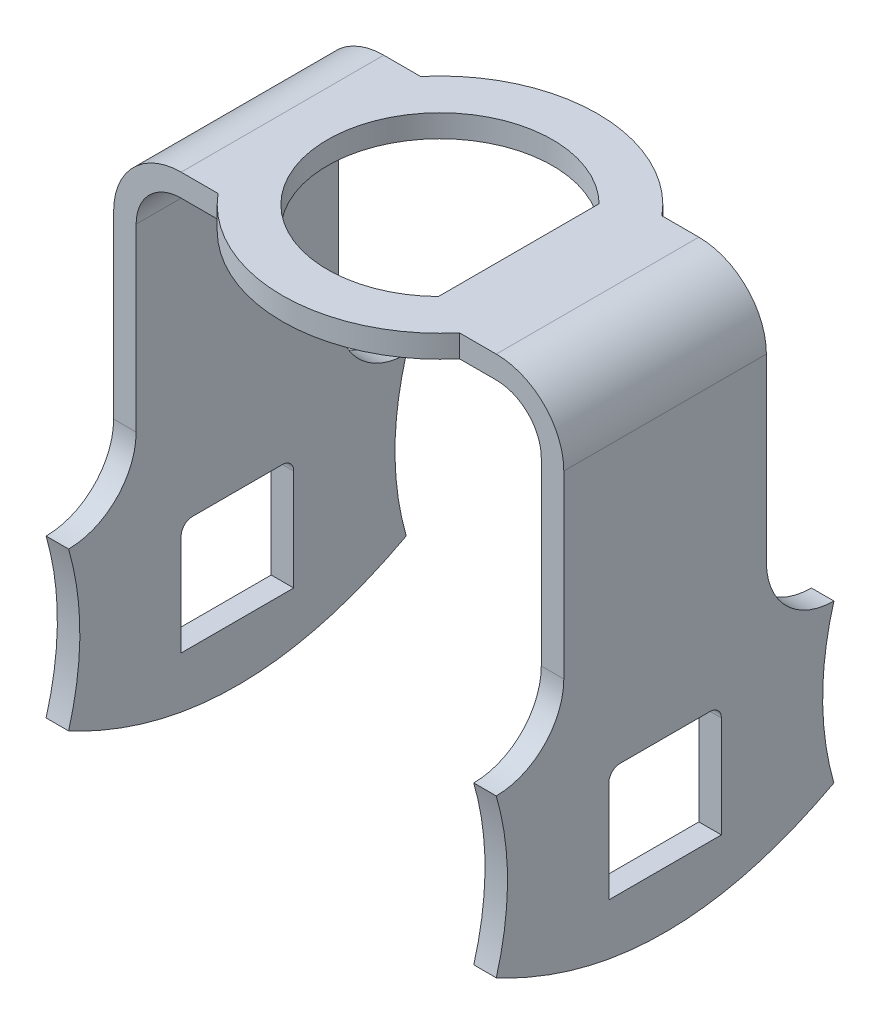
SolidWorks part; units mm, degrees
ref_plane "Front Plane" through (0, 0, 0) normal (0, 0, 1) x (1, 0, 0)
ref_plane "Top Plane" through (0, 0, 0) normal (0, 1, 0) x (1, 0, 0)
ref_plane "Right Plane" through (0, 0, 0) normal (1, 0, 0) x (0, 0, -1)
sketch "Sketch1" plane through (0, 0, 0) normal (0, 0, 1) x (1, 0, 0)
  line L0 (-19, 0) -> (-19, 20)
  line L1 (0, 0) -> (-1, 0)
  line L2 (0, 0) -> (0, 20)
  line L3 (-3, 23) -> (-17, 23)
  line L4 (-20, 0) -> (-20, 20)
  line L5 (-3, 22) -> (-17, 22)
  line L6 (-1, 0) -> (-1, 20)
  line L7 (-19, 0) -> (-20, 0)
  arc A0 (-17, 23) -> (-20, 20) centre (-17, 20) ccw
  arc A1 (0, 20) -> (-3, 23) centre (-3, 20) ccw
  arc A2 (-17, 22) -> (-19, 20) centre (-17, 20) ccw
  arc A3 (-1, 20) -> (-3, 22) centre (-3, 20) ccw
  point P7 (-20, 23)
  point P10 (0, 23)
  dimension "D3" = 3
  dimension "D4" = 3
  dimension "D1" = 23
  dimension "D2" = 20
  dimension "D5" = 1
extrude "Boss-Extrude1" add sketch "Sketch1" along normal blind 15
sketch "Sketch2" plane through (0, 23, 0) normal (0, 1, 0) x (1, 0, 0)
  line L0 (-10, 0) -> (-10, -15) construction
  line L1 (-3, 0) -> (-17, 0) construction
  line L2 (-3, -15) -> (-17, -15) construction
  line L3 (-6.5, -11.0707) -> (-6.5, -3.9293)
  arc A0 (-6.5, -3.9293) -> (-6.5, -11.0707) centre (-10, -7.5) ccw
  dimension "D1" = 10
  dimension "D2" = 3.5
extrude "Cut-Extrude2" cut sketch "Sketch2" against normal through all
sketch "Sketch4" plane through (0, 23, 0) normal (0, 1, 0) x (1, 0, 0)
  line L0 (0, -7.5) -> (-20, -7.5) construction
  line L1 (0, -15) -> (0, 0) construction
  line L2 (-20, -15) -> (-20, 0) construction
  line L3 (-4.6381, -12) -> (0, -12)
  line L4 (-4.6381, -3) -> (0, -3)
  line L5 (-10, 0) -> (-10, -15) construction
  line L6 (-3, 0) -> (-17, 0) construction
  line L7 (-3, -15) -> (-17, -15) construction
  line L8 (-15.3619, -12) -> (-20, -12)
  line L9 (-15.3619, -3) -> (-20, -3)
  line L10 (-20, -3) -> (-20, 0)
  line L11 (-20, 0) -> (0, 0)
  line L12 (0, 0) -> (0, -3)
  line L13 (-20, -12) -> (-20, -15)
  line L14 (-20, -15) -> (0, -15)
  line L15 (0, -15) -> (0, -12)
  arc A0 (-15.3619, -12) -> (-4.6381, -12) centre (-10, -7.5) ccw
  arc A1 (-4.6381, -3) -> (-15.3619, -3) centre (-10, -7.5) ccw
  dimension "D1" = 14
  dimension "D2" = 4.5
  dimension "D3" = 4.5
extrude "Cut-Extrude3" cut sketch "Sketch4" against normal blind 14
sketch "Sketch5" plane through (-20, 0, 0) normal (-1, 0, 0) x (0, 0, 1)
  line L0 (15, 0) -> (0, 0) construction
  line L1 (0, 0) -> (0, 2)
  line L2 (0, 9) -> (0, 0) construction
  line L3 (15, 9) -> (15, 0) construction
  line L4 (0, 2) -> (0, 0)
  line L5 (15, 0) -> (15, 2)
  spline S0 degree 2 poles (0, 2) (7.5, -2) (15, 2) knots 0 0 0 1 1 1
  point P0 (7.5, 0)
  line M6 (0, 9) -> (0, 0)
  line M7 (0, 0) -> (15, 0)
  line M8 (15, 0) -> (15, 9)
  dimension "D1" = 2
  dimension "D2" = 2
extrude "Cut-Extrude4" cut sketch "Sketch5" against normal through all contours S0 M6 M7 | S0 M7 M8 region at (-20, 0.6, 13.125) region at (-20, 0.6, 1.875)
sketch "Sketch6" plane through (-20, 0, 0) normal (-1, 0, 0) x (0, 0, 1)
  line L0 (0, 9) -> (0, 2) construction
  line L1 (0, 5.5) -> (0.5, 5.5)
  line L2 (7.5, 0) -> (7.5, 13.8761) construction
  line L3 (15, 2) -> (15, 9) construction
  line L4 (0, 9) -> (0, 2)
  line L5 (15, 9) -> (15, 2)
  parabola Q0 (0, 2) -> (15, 2) focus (7.5, 7.0312) apex (7.5, 0) construction
  spline S0 degree 2 poles (0, 9) (1, 5.5) (0, 2) knots 0 0 0 1 1 1
  spline S1 degree 2 poles (15, 9) (14, 5.5) (15, 2) knots 0 0 0 1 1 1
  point P0 (0, 5.5)
  point P19 (15, 5.5)
  line M8 (0, 9) -> (0, 2)
  dimension "D1" = 0.5
  dimension "D2" = 0.5
extrude "Cut-Extrude5" cut sketch "Sketch6" against normal through all contours S0 L1 M8 | L4 S0 | L5 S1 region at (-20, 6.8125, 0.2)
fillet "Fillet1" radius 3 1 edges at (-19.5, 9, 3)
fillet "Fillet2" radius 3 3 edges at (-0.5, 9, 3) (-0.5, 9, 12) (-19.5, 9, 12)
sketch "Sketch7" plane through (-20, 0, 0) normal (-1, 0, 0) x (0, 0, 1)
  line L1 (5, 7.5) -> (10, 7.5)
  line L2 (5, 7.5) -> (5, 2.5)
  line L3 (5, 2.5) -> (10, 2.5)
  line L4 (10, 7.5) -> (10, 2.5)
  line L5 (0.5, 22) -> (3, 22) construction
  line L6 (7.5, 0) -> (7.5, 15) construction
  parabola Q0 (0, 2) -> (15, 2) focus (7.5, 7.0312) apex (7.5, 0) construction
  point P4 (1.75, 22)
  point P13 (7.5, 7.5)
  dimension "D1" = 19.5
  dimension "D2" = 5
  dimension "D3" = 5
extrude "Cut-Extrude6" cut sketch "Sketch7" against normal through all
fillet "Fillet3" radius 0.5 4 edges at (-0.5, 7.5, 10) (-0.5, 7.5, 5) (-19.5, 7.5, 10) (-19.5, 7.5, 5)
